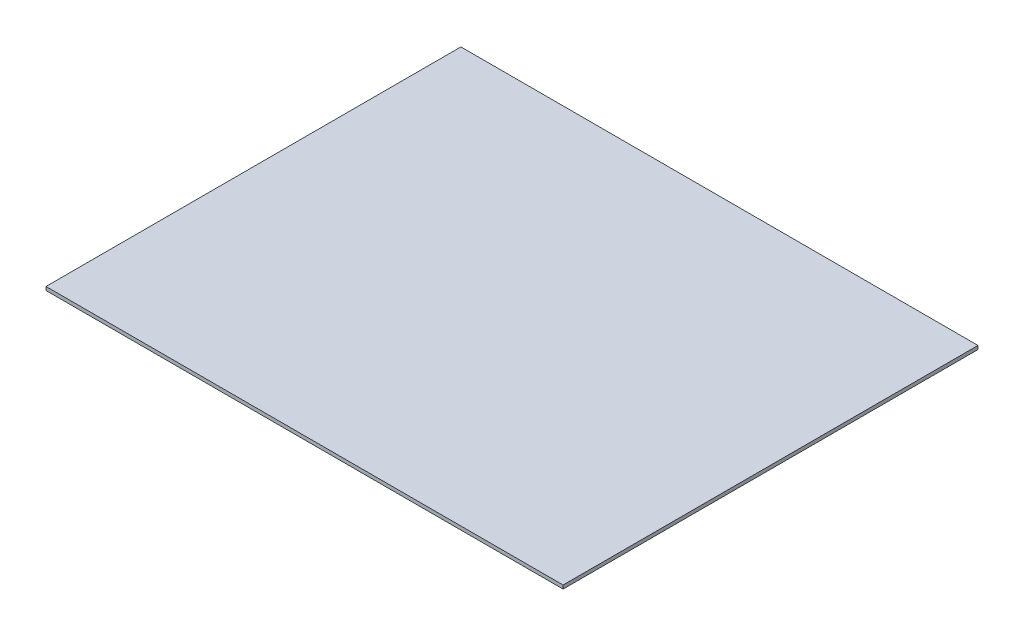
SolidWorks part; units mm, degrees
ref_plane "Front Plane" through (0, 0, 0) normal (0, 0, 1) x (1, 0, 0)
ref_plane "Top Plane" through (0, 0, 0) normal (0, 1, 0) x (1, 0, 0)
ref_plane "Right Plane" through (0, 0, 0) normal (1, 0, 0) x (0, 0, -1)
sketch "Sketch1" plane through (0, 0, 0) normal (0, 1, 0) x (1, 0, 0)
  line L1 (-124, 99.5) -> (124, 99.5)
  line L2 (-124, 99.5) -> (-124, -99.5)
  line L3 (-124, -99.5) -> (124, -99.5)
  line L4 (124, 99.5) -> (124, -99.5)
  line L5 (-124, 99.5) -> (124, -99.5) construction
  line L6 (-124, -99.5) -> (124, 99.5) construction
  point P0 (0, 0)
  dimension "D1" = 199
  dimension "D2" = 248
extrude "Boss-Extrude1" add sketch "Sketch1" along normal blind 1.7
